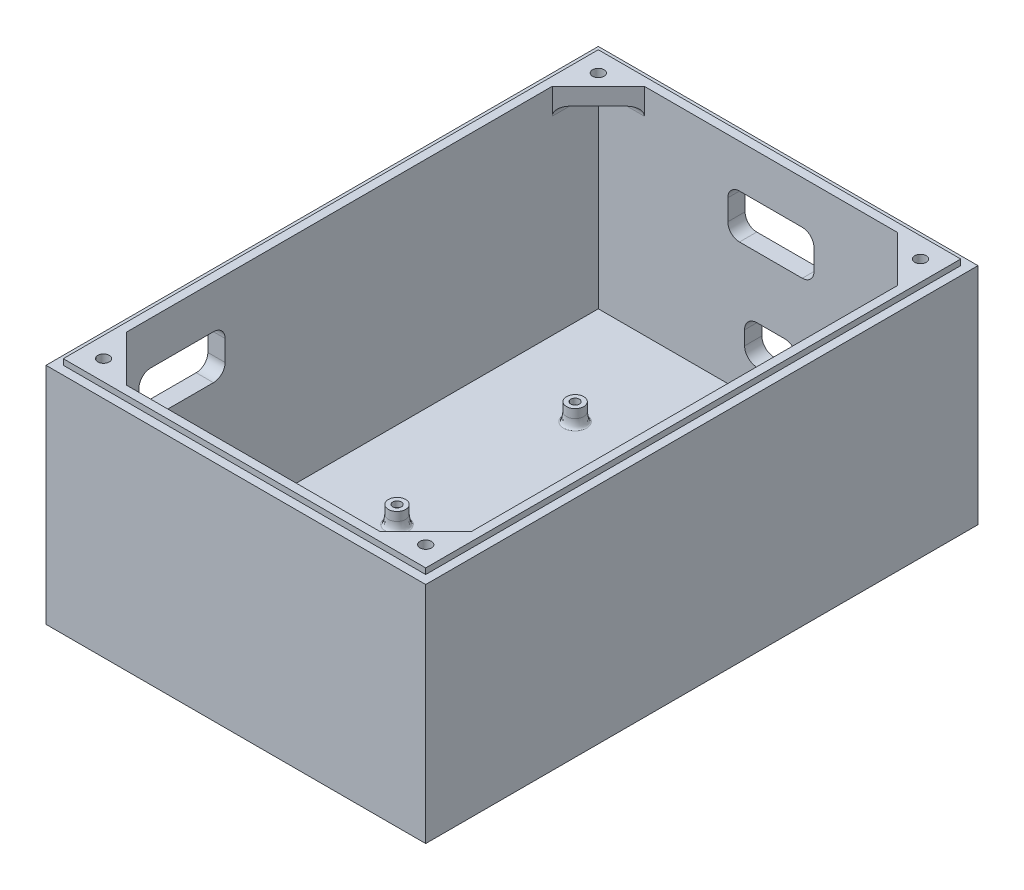
SolidWorks part; units mm, degrees
ref_plane "Front Plane" through (0, 0, 0) normal (0, 0, 1) x (1, 0, 0)
ref_plane "Top Plane" through (0, 0, 0) normal (0, 1, 0) x (1, 0, 0)
ref_plane "Right Plane" through (0, 0, 0) normal (1, 0, 0) x (0, 0, -1)
sketch "Sketch1" plane through (0, 0, 0) normal (0, 1, 0) x (1, 0, 0)
  line L0 (-60, 0) -> (60, 0) construction
  line L1 (-60, 90) -> (60, 90)
  line L2 (-60, 90) -> (-60, -90)
  line L3 (-60, -90) -> (60, -90)
  line L4 (60, 90) -> (60, -90)
  line L6 (-66, 96) -> (66, 96)
  line L7 (-66, 96) -> (-66, -96)
  line L8 (-66, -96) -> (66, -96)
  line L9 (66, 96) -> (66, -96)
  line L10 (-66, 96) -> (66, -96) construction
  line L11 (-66, -96) -> (66, 96) construction
  point P4 (0, 0)
  dimension "D1" = 120
  dimension "D2" = 180
  dimension "D3" = 6
  dimension "D4" = 6
extrude "Boss-Extrude1" add sketch "Sketch1" along normal blind 80
sketch "Sketch2" plane through (0, 0, 0) normal (0, -1, 0) x (-1, 0, 0)
  line L1 (66, 96) -> (-66, 96)
  line L2 (66, 96) -> (66, -96)
  line L3 (66, -96) -> (-66, -96)
  line L4 (-66, 96) -> (-66, -96)
extrude "Boss-Extrude2" add sketch "Sketch2" against normal blind 5
sketch "Sketch3" plane through (0, 0, -96) normal (0, 0, -1) x (-1, 0, 0)
  line L0 (0, 80) -> (0, 0) construction
  line L5 (-66, 80) -> (66, 80) construction
  line L6 (-66, 0) -> (66, 0) construction
  line L7 (-10.915, 65) -> (10.915, 65)
  line L8 (-14.975, 60.94) -> (-14.975, 53.72)
  line L9 (-10.915, 49.66) -> (10.915, 49.66)
  line L10 (14.975, 60.94) -> (14.975, 53.72)
  line L11 (-14.975, 65) -> (14.975, 49.66) construction
  line L12 (-14.975, 49.66) -> (14.975, 65) construction
  line L13 (-4.875, 28.38) -> (4.875, 28.38)
  line L14 (-9.145, 24.11) -> (-9.145, 19.27)
  line L15 (-4.875, 15) -> (4.875, 15)
  line L16 (9.145, 24.11) -> (9.145, 19.27)
  line L17 (-9.145, 28.38) -> (9.145, 15) construction
  line L18 (-9.145, 15) -> (9.145, 28.38) construction
  arc A0 (-9.145, 19.27) -> (-4.875, 15) centre (-4.875, 19.27) ccw
  arc A1 (4.875, 15) -> (9.145, 19.27) centre (4.875, 19.27) ccw
  arc A2 (4.875, 28.38) -> (9.145, 24.11) centre (4.875, 24.11) cw
  arc A3 (-4.875, 28.38) -> (-9.145, 24.11) centre (-4.875, 24.11) ccw
  arc A4 (-14.975, 53.72) -> (-10.915, 49.66) centre (-10.915, 53.72) ccw
  arc A5 (10.915, 49.66) -> (14.975, 53.72) centre (10.915, 53.72) ccw
  arc A6 (10.915, 65) -> (14.975, 60.94) centre (10.915, 60.94) cw
  arc A7 (-10.915, 65) -> (-14.975, 60.94) centre (-10.915, 60.94) ccw
  point P0 (0, 57.33)
  point P10 (0, 21.69)
  dimension "D7" = 4.27
  dimension "D8" = 4.06
  dimension "D1" = 15.34
  dimension "D2" = 29.95
  dimension "D3" = 13.38
  dimension "D4" = 18.29
  dimension "D5" = 15
  dimension "D6" = 15
extrude "Cut-Extrude1" cut sketch "Sketch3" against normal up to surface (6 mm away) up to face at (0, 42.5, -90)
sketch "Sketch4" plane through (-66, 0, 0) normal (-1, 0, 0) x (0, 0, 1)
  line L0 (54.7107, 80) -> (54.7107, 0) construction
  line L1 (43.7957, 65) -> (65.6257, 65)
  line L2 (39.7357, 60.94) -> (39.7357, 53.72)
  line L3 (43.7957, 49.66) -> (65.6257, 49.66)
  line L10 (69.6857, 60.94) -> (69.6857, 53.72)
  line L11 (39.7357, 65) -> (69.6857, 49.66) construction
  line L16 (39.7357, 49.66) -> (69.6857, 65) construction
  line L17 (49.8357, 28.38) -> (59.5857, 28.38)
  line L18 (45.5657, 24.11) -> (45.5657, 19.27)
  line L19 (49.8357, 15) -> (59.5857, 15)
  line L20 (63.8557, 24.11) -> (63.8557, 19.27)
  line L21 (45.5657, 28.38) -> (63.8557, 15) construction
  line L22 (45.5657, 15) -> (63.8557, 28.38) construction
  line L23 (-96, 0) -> (96, 0) construction
  line L24 (-96, 80) -> (96, 80) construction
  arc A0 (45.5657, 19.27) -> (49.8357, 15) centre (49.8357, 19.27) ccw
  arc A1 (59.5857, 15) -> (63.8557, 19.27) centre (59.5857, 19.27) ccw
  arc A2 (59.5857, 28.38) -> (63.8557, 24.11) centre (59.5857, 24.11) cw
  arc A3 (49.8357, 28.38) -> (45.5657, 24.11) centre (49.8357, 24.11) ccw
  arc A4 (39.7357, 53.72) -> (43.7957, 49.66) centre (43.7957, 53.72) ccw
  arc A5 (65.6257, 49.66) -> (69.6857, 53.72) centre (65.6257, 53.72) ccw
  arc A6 (65.6257, 65) -> (69.6857, 60.94) centre (65.6257, 60.94) cw
  arc A7 (43.7957, 65) -> (39.7357, 60.94) centre (43.7957, 60.94) ccw
  point P0 (54.7107, 57.33)
  point P7 (54.7107, 21.69)
  dimension "D5" = 4.27
  dimension "D6" = 4.06
  dimension "D1" = 15.34
  dimension "D2" = 29.95
  dimension "D3" = 13.38
  dimension "D4" = 18.29
  dimension "D7" = 15
  dimension "D8" = 15
extrude "Cut-Extrude2" cut sketch "Sketch4" against normal up to surface (6 mm away) up to face at (-60, 42.5, 0)
sketch "Sketch5" plane through (0, 5, 0) normal (0, 1, 0) x (1, 0, 0)
  line L1 (-30.089, 52.032) -> (42.047, 52.032)
  line L2 (-30.089, 52.032) -> (-30.089, -71.793)
  line L3 (-30.089, -71.793) -> (42.047, -71.793)
  line L4 (42.047, 52.032) -> (42.047, -71.793)
  circle A0 centre (-30.089, 52.032) radius 3
  circle A1 centre (42.047, 52.032) radius 3
  circle A2 centre (-30.089, -71.793) radius 3
  circle A3 centre (42.047, -71.793) radius 3
  circle A5 centre (-30.089, -9.8805) radius 3
  circle A6 centre (42.047, -9.8805) radius 3
  dimension "D1" = 6
extrude "Boss-Extrude3" add sketch "Sketch5" along normal blind 6 contours L4 A1 L1 | L1 A1 L4 | L3 A3 L4 | L4 A3 L3 | L1 A0 L2 | L2 A0 L1 | L3 A2 L2 | L2 A2 L3 | L2 A5 | L2 A5 | L4 A6 | L4 A6 region at (-30.5134, 5, -52.4564) region at (-28.8158, 5, -50.7588) region at (42.4714, 5, -52.4564) region at (40.7738, 5, -50.7588) region at (-28.8158, 5, 9.8805) region at (-31.3622, 5, 9.8805) region at (43.3202, 5, 9.8805) region at (40.7738, 5, 9.8805) region at (-28.8158, 5, 70.5198) region at (-30.5134, 5, 72.2174) region at (42.4714, 5, 72.2174) region at (40.7738, 5, 70.5198)
fillet "Fillet2" radius 1 6 edges at (-30.089, 5, 74.793) (-30.089, 5, 12.8805) (-30.089, 5, -49.032) (42.047, 5, 74.793) (42.047, 5, 12.8805) (42.047, 5, -49.032) second distance 3 first distance on face at (42.047, 5, 12.8805)
sketch "Sketch7" plane through (0, 80, 0) normal (0, 1, 0) x (1, 0, 0)
  line L0 (-60, 0) -> (60, 0) construction
  line L1 (-60, 90) -> (-52, 90)
  line L2 (-60, 90) -> (-60, 82)
  line L3 (-60, 82) -> (-52, 82)
  line L4 (-52, 90) -> (-52, 82)
  line L5 (-60, 90) -> (-60, -90) construction
  line L6 (60, -90) -> (60, 90) construction
  line L7 (-52, -90) -> (-52, -82)
  line L8 (-60, -82) -> (-52, -82)
  line L9 (-60, -90) -> (-60, -82)
  line L10 (-60, -90) -> (-52, -90)
  line L11 (0, 90) -> (0, -90) construction
  line L16 (60, 90) -> (-60, 90) construction
  line L17 (-60, -90) -> (60, -90) construction
  line L22 (60, -90) -> (52, -90)
  line L23 (60, -90) -> (60, -82)
  line L24 (60, -82) -> (52, -82)
  line L25 (52, -90) -> (52, -82)
  line L26 (52, 90) -> (52, 82)
  line L27 (60, 82) -> (52, 82)
  line L28 (60, 90) -> (60, 82)
  line L29 (60, 90) -> (52, 90)
  line L30 (-56, 90) -> (-56, 82) construction
  line L31 (-60, 86) -> (-52, 86) construction
  line L32 (-60, -82) -> (-52, -90) construction
  line L33 (52, -82) -> (60, -90) construction
  line L34 (-44, 90) -> (-60, 74)
  line L35 (60, 90) -> (-60, 90) construction
  line L36 (44, 90) -> (60, 74)
  line L37 (44, -90) -> (60, -74)
  line L38 (-44, -90) -> (-60, -74)
  circle A0 centre (-56, 86) radius 2
  circle A1 centre (56, 86) radius 2
  circle A3 centre (56, -86) radius 2
  circle A5 centre (-56, -86) radius 2
  circle A6 centre (-56, 0) radius 2 [skipped]
  circle A7 centre (56, 0) radius 2 [skipped]
  point P17 (-52, 82)
  point P43 (56, -86)
  point P45 (-56, -86)
  line M13 (60, -90) -> (-60, -90)
  line M14 (-60, -90) -> (-60, 90)
  line M15 (-60, 90) -> (60, 90)
  line M16 (60, 90) -> (60, -90)
  dimension "D5" = 4
  dimension "D1" = 8
  dimension "D2" = 8
  dimension "D6" = 2
  dimension "D7" = 3
extrude "Boss-Extrude4" add sketch "Sketch7" against normal blind 6 contours L4 L3 A0 M15 M14 | L34 L3 M14 | L34 L4 M15 | L36 L26 M15 | L27 L26 A1 M16 M15 | L27 L36 M16 | L37 L25 M13 | L25 L24 A3 M13 M16 | L37 L24 M16 | L8 L7 A5 M14 M13 | L8 L38 M14 | L38 L7 M13 region at (-56, 80, -89.8869) region at (-49.3333, 80, -87.3333) region at (-57.3333, 80, -79.3333) region at (49.3333, 80, -87.3333) region at (-57.3333, 80, 79.3333) region at (52.1131, 80, -86) region at (57.3333, 80, -79.3333) region at (-49.3333, 80, 87.3333) region at (-52.1131, 80, 86) region at (57.3333, 80, 79.3333) region at (49.3333, 80, 87.3333) region at (56, 80, 82.1131)
sketch "Sketch9" plane through (0, 80, 0) normal (0, 1, 0) x (1, 0, 0)
  line L5 (-66, 96) -> (66, 96)
  line L6 (-66, 96) -> (-66, -96)
  line L7 (-66, -96) -> (66, -96)
  line L8 (-63, -93) -> (63, -93)
  line L9 (63, -93) -> (63, 93)
  line L10 (-63, 93) -> (-63, -93)
  line L11 (63, 93) -> (-63, 93)
  line L12 (-63, -93) -> (63, -93)
  line L13 (63, -93) -> (63, 93)
  line L14 (-63, 93) -> (-63, -93)
  line L15 (63, 93) -> (-63, 93)
  line L16 (66, 96) -> (66, -96)
  dimension "D1" = 3
extrude "Cut-Extrude3" cut sketch "Sketch9" against normal blind 2
fillet "Fillet5" radius 3 8 edges at (52, 74, 90) (60, 74, 82) (60, 74, -82) (52, 74, -90) (-60, 74, 82) (-52, 74, 90) (-52, 74, -90) (-60, 74, -82)
sketch "Sketch10" plane through (0, 11, 0) normal (0, 1, 0) x (1, 0, 0)
  circle A0 centre (-30.089, 52.032) radius 1.5
  circle A1 centre (42.047, 52.032) radius 1.5
  circle A2 centre (42.047, -9.8805) radius 1.5
  circle A3 centre (42.047, -71.793) radius 1.5
  circle A4 centre (-30.089, -71.793) radius 1.5
  circle A5 centre (-30.089, -9.8805) radius 1.5
  dimension "D1" = 3
extrude "Cut-Extrude4" cut sketch "Sketch10" against normal blind 2
equation "\"length\"= 120"
equation "\"D1@Sketch1\"=\"length\""
equation "\"width\"= 180"
equation "\"D2@Sketch1\"=\"width\""
equation "\"wall_thickness\"= 6"
equation "\"D3@Sketch1\"=\"wall_thickness\""
equation "\"D4@Sketch1\"=\"wall_thickness\""
equation "\"hieght\"= 80"
equation "\"D1@Boss-Extrude1\"=\"hieght\""
equation "\"base_thickness\"= 5"
equation "\"D1@Boss-Extrude2\"=\"base_thickness\""
